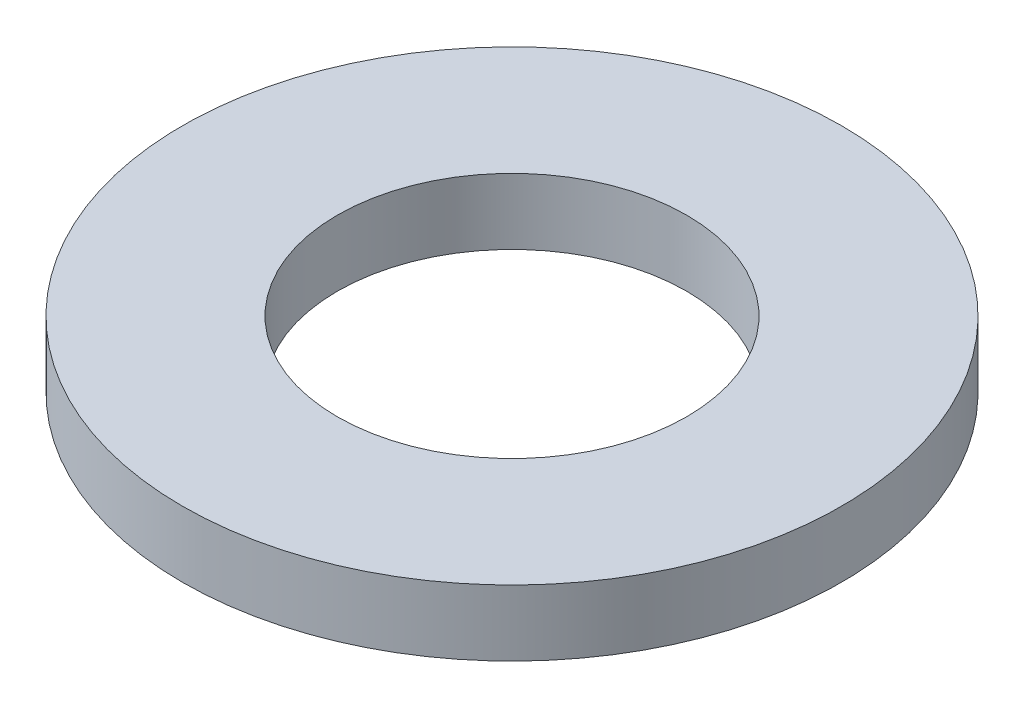
SolidWorks part; units mm, degrees
ref_plane "Face" through (0, 0, 0) normal (0, 0, 1) x (1, 0, 0)
ref_plane "Dessus" through (0, 0, 0) normal (0, 1, 0) x (1, 0, 0)
ref_plane "Droite" through (0, 0, 0) normal (1, 0, 0) x (0, 0, -1)
ref_axis "Axe1" through (0, 6.1904, 0) along (0, -1, 0)
sketch "Esquisse1" plane through (0, 0, 0) normal (0, 0, 1) x (1, 0, 0)
  line L1 (0, 0) -> (0, 2.5443) construction
  line L2 (2.65, 0) -> (2.65, 1)
  line L3 (2.65, 0) -> (5, 0)
  line L4 (5, 0) -> (5, 1)
  line L5 (5, 1) -> (2.65, 1)
  line L6 (2.65, 0) -> (-2.65, 0) construction
  line L7 (5, 0) -> (-5, 0) construction
  dimension "Epaisseur" = 1
  dimension "Diamètre de passage" = 5.3
  dimension "Diamètre extérieur" = 10
revolve "Base-Révolution" add sketch "Esquisse1" angle 360 about L1
